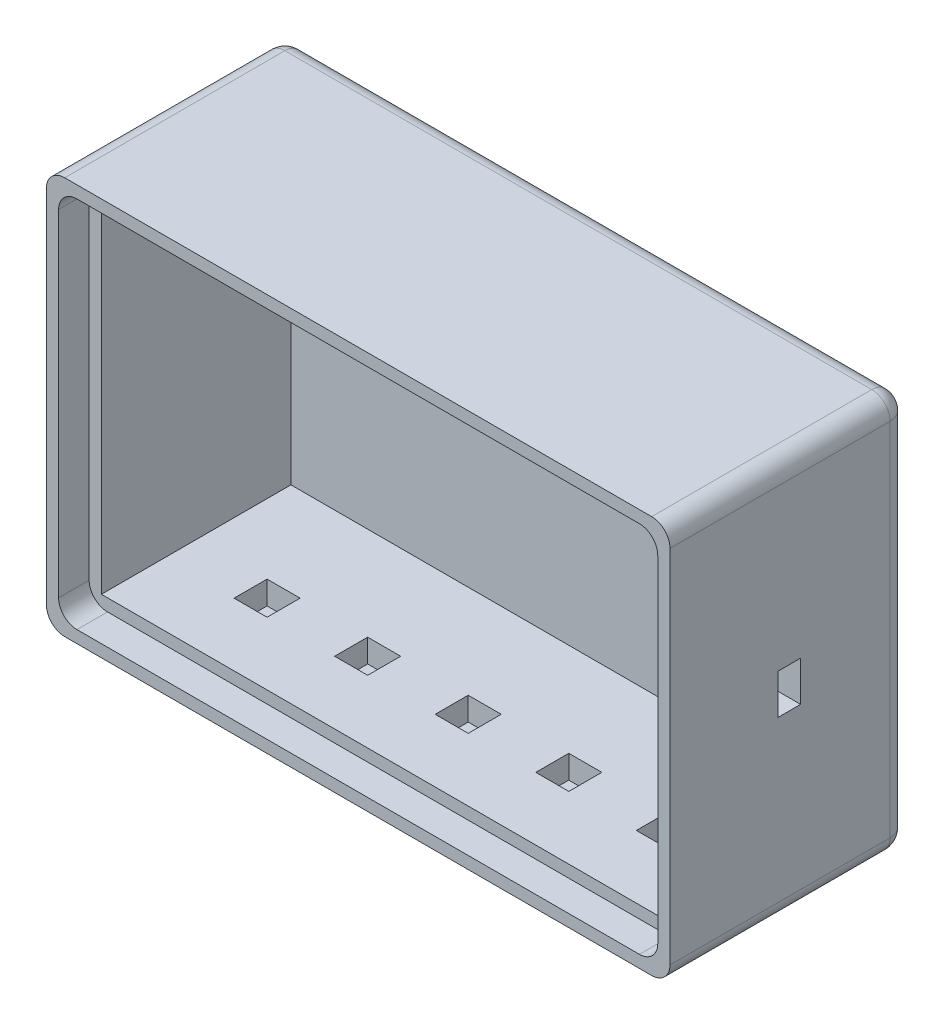
SolidWorks part; units mm, degrees
ref_plane "Přední rovina" through (0, 0, 0) normal (0, 0, 1) x (1, 0, 0)
ref_plane "Horní rovina" through (0, 0, 0) normal (0, 1, 0) x (1, 0, 0)
ref_plane "Pravá rovina" through (0, 0, 0) normal (1, 0, 0) x (0, 0, -1)
sketch "Skica1" plane through (0, 0, 0) normal (0, 0, 1) x (1, 0, 0)
  line L1 (0, 0) -> (98, 0)
  line L2 (0, 0) -> (0, 61)
  line L3 (0, 61) -> (98, 61)
  line L4 (98, 0) -> (98, 61)
  line L5 (-2, 63) -> (100, 63)
  line L6 (-2, 63) -> (-2, -2)
  line L7 (-2, -2) -> (100, -2)
  line L8 (100, 63) -> (100, -2)
  line L9 (2, 59) -> (96, 59)
  line L10 (2, 59) -> (2, 2)
  line L11 (2, 2) -> (96, 2)
  line L12 (96, 59) -> (96, 2)
  dimension "D1" = 102
  dimension "D2" = 65
  dimension "D3" = 2
  dimension "D4" = 2
  dimension "D5" = 2
  dimension "D6" = 2
  dimension "D7" = 2
  dimension "D8" = 2
  dimension "D9" = 2
  dimension "D10" = 2
  dimension "D11" = 57
  dimension "D12" = 94
extrude "Přidat vysunutím1" add sketch "Skica1" along normal blind 3 contours L6 L7 L8 L5
extrude "Přidat vysunutím2" add sketch "Skica1<4>" along normal blind 39 contours L8 L5 L6 L7 L4 L1 L2 L3 region at (49, 61.7905, 0)
sketch "Skica1<4>" plane through (0, 0, 0) normal (0, 0, 1) x (1, 0, 0) same geometry as "Skica1"
extrude "Přidat vysunutím3" add sketch "Skica1<5>" along normal blind 34 contours L1 L4 L3 L2 L9 L12 L11 L10 region at (1.1543, 30.5, 0)
sketch "Skica1<5>" plane through (0, 0, 0) normal (0, 0, 1) x (1, 0, 0) same geometry as "Skica1"
sketch "Skica2" plane through (100, 0, 0) normal (1, 0, 0) x (0, 0, -1)
  line L0 (-19.5, 63) -> (-19.5, -2) construction
  line L1 (-21.365, 27.225) -> (-17.635, 27.225)
  line L2 (-21.365, 27.225) -> (-21.365, 33.775)
  line L3 (-21.365, 33.775) -> (-17.635, 33.775)
  line L4 (-17.635, 27.225) -> (-17.635, 33.775)
  line L5 (-21.365, 27.225) -> (-17.635, 33.775) construction
  line L6 (-21.365, 33.775) -> (-17.635, 27.225) construction
  line L7 (-39, 63) -> (0, 63) construction
  line L8 (-39, -2) -> (0, -2) construction
  line L9 (-39, 30.5) -> (0, 30.5) construction
  line L10 (-39, 63) -> (-39, -2) construction
  line L11 (0, 63) -> (0, -2) construction
  point P0 (-19.5, 30.5)
  point P17 (-19.5, 30.5)
  dimension "D1" = 6.55
  dimension "D2" = 3.73
extrude "Odebrat vysunutím1" cut sketch "Skica2" against normal up to surface (4 mm away) up to face at (96, 30.5, 18.5)
fillet "Zaoblit1" radius 3 4 edges at (-2, 30.5, 0) (49, 63, 0) (100, 30.5, 0) (49, -2, 0)
sketch "Skica4" plane through (0, -2, 0) normal (0, -1, 0) x (1, 0, 0)
  line L0 (-2, 39) -> (-2, 3) construction
  line L1 (13.4, 23.7) -> (18.8, 23.7)
  line L2 (13.4, 23.7) -> (13.4, 18.3)
  line L3 (13.4, 18.3) -> (18.8, 18.3)
  line L4 (18.8, 23.7) -> (18.8, 18.3)
  line L5 (-2, 21) -> (100, 21) construction
  line L6 (100, 39) -> (100, 3) construction
  line L7 (-2, 39) -> (100, 39) construction
  line L8 (29.85, 23.7) -> (35.25, 23.7)
  line L9 (29.85, 23.7) -> (29.85, 18.3)
  line L10 (29.85, 18.3) -> (35.25, 18.3)
  line L11 (35.25, 23.7) -> (35.25, 18.3)
  line L12 (46.3, 23.7) -> (51.7, 23.7)
  line L13 (46.3, 23.7) -> (46.3, 18.3)
  line L14 (46.3, 18.3) -> (51.7, 18.3)
  line L15 (51.7, 23.7) -> (51.7, 18.3)
  line L16 (62.75, 23.7) -> (68.15, 23.7)
  line L17 (62.75, 23.7) -> (62.75, 18.3)
  line L18 (62.75, 18.3) -> (68.15, 18.3)
  line L19 (68.15, 23.7) -> (68.15, 18.3)
  line L20 (79.2, 23.7) -> (84.6, 23.7)
  line L21 (79.2, 23.7) -> (79.2, 18.3)
  line L22 (79.2, 18.3) -> (84.6, 18.3)
  line L23 (84.6, 23.7) -> (84.6, 18.3)
  line L24 (49, 39) -> (49, 3) construction
  line L25 (-2, 3) -> (100, 3) construction
  point P12 (13.4, 21)
  dimension "D1" = 5.4
  dimension "D2" = 5.4
  dimension "D4" = 5.4
  dimension "D5" = 5.4
  dimension "D6" = 5.4
  dimension "D7" = 5.4
  dimension "D8" = 11.05
  dimension "D9" = 11.05
  dimension "D10" = 11.05
  dimension "D11" = 11.05
fillet "Zaoblit2" radius 3 8 edges at (-1.1213, 62.1213, 0.8787) (99.1213, 62.1213, 0.8787) (99.1213, -1.1213, 0.8787) (-1.1213, -1.1213, 0.8787) (-2, 63, 21) (100, 63, 21) (100, -2, 21) (-2, -2, 21)
extrude "Odebrat vysunutím2" cut sketch "Skica4" against normal up to surface (4 mm away) from offset 0.2 up to face at (49, 2, 18.5) offset against normal yes
fillet "Zaoblit3" radius 3 4 edges at (98, 0, 36.5) (0, 0, 36.5) (0, 61, 36.5) (98, 61, 36.5)
